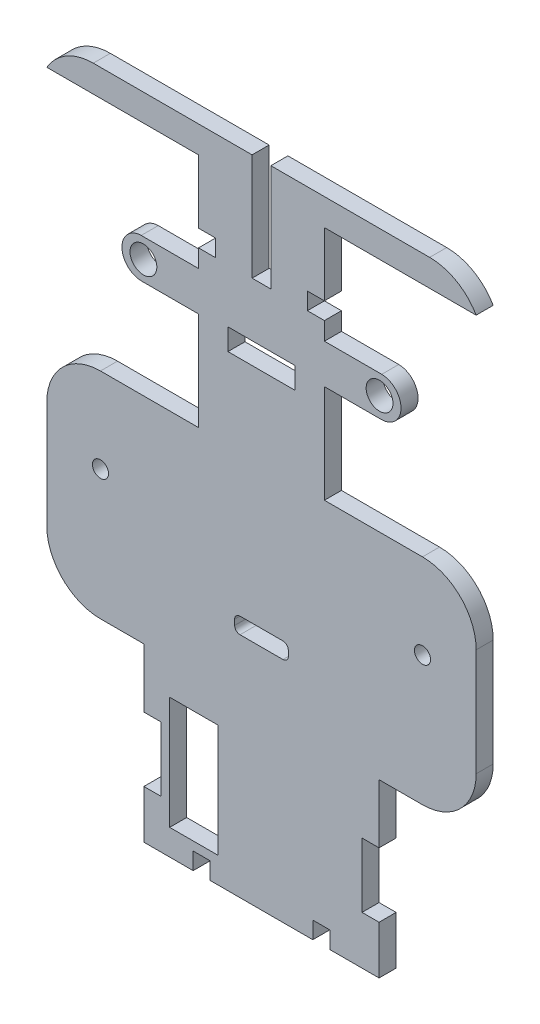
SolidWorks part; units mm, degrees
ref_plane "Front Plane" through (0, 0, 0) normal (0, 0, 1) x (1, 0, 0)
ref_plane "Top Plane" through (0, 0, 0) normal (0, 1, 0) x (1, 0, 0)
ref_plane "Right Plane" through (0, 0, 0) normal (1, 0, 0) x (0, 0, -1)
sketch "Sketch1" plane through (0, 0, 0) normal (0, 0, 1) x (1, 0, 0)
  line L0 (0, 41.2415) -> (0, -44.2517) construction
  line L1 (-63.3907, 0) -> (63.762, 0) construction
  line L2 (-9.56, -41.4376) -> (9.56, -41.4376)
  line L3 (21.91, -41.4376) -> (21.91, -32.4376)
  line L4 (21.91, -9.4376) -> (40, -9.4376)
  line L5 (40, -9.4376) -> (40, 30.5624)
  line L6 (40, 30.5624) -> (10, 30.5624)
  line L7 (10, 30.5624) -> (10, 45.5624)
  line L8 (12.735, -31.7231) -> (12.735, -41.4376) construction
  line L9 (-10, 59.5624) -> (-8.5528, 59.5624)
  line L10 (10, 59.5624) -> (8.5528, 59.5624)
  line L11 (11.7278, 62.7374) -> (11.7278, 74.5624)
  line L12 (11.7278, 74.5624) -> (40, 74.5624)
  line L13 (40, 74.5624) -> (40, 79.5624)
  line L14 (-40, 79.5624) -> (40, 79.5624)
  line L15 (0, 41.2415) -> (0, 85.4214) construction
  line L16 (22, 52.5624) -> (-14.5, 52.5624) construction
  line L17 (8.5528, 59.5624) -> (8.5528, 62.7374)
  line L18 (8.5528, 62.7374) -> (11.7278, 62.7374)
  line L19 (15.91, -41.4376) -> (21.91, -41.4376)
  line L20 (12.735, -41.4376) -> (12.735, -38.2626)
  line L21 (22, 50.0624) -> (22, 45.5624) construction
  line L22 (-10, 45.5624) -> (-10, 48.8958)
  line L23 (12.735, -38.2626) -> (9.56, -38.2626)
  line L24 (21.91, -20.4376) -> (21.91, -9.4376)
  line L25 (10, 59.5624) -> (-10, 59.5624) construction
  line L26 (21.91, -20.4376) -> (18.735, -20.4376)
  line L27 (18.735, -20.4376) -> (18.735, -32.4376)
  line L28 (18.735, -32.4376) -> (21.91, -32.4376)
  line L29 (9.56, -38.2626) -> (9.56, -41.4376)
  line L30 (12.735, -41.4376) -> (15.91, -41.4376)
  line L31 (21.91, -9.4376) -> (21.91, 2.5624) construction
  line L32 (-11.7278, 56.229) -> (-22.4103, 56.229)
  line L33 (-12.735, -31.7231) -> (-12.735, -41.4376) construction
  line L34 (11.7278, 62.7374) -> (11.7278, 56.229) construction
  line L35 (-19.5, 52.5624) -> (-22, 52.5624) construction
  line L36 (-12.735, -41.4376) -> (-15.91, -41.4376)
  line L37 (-9.56, -38.2626) -> (-9.56, -41.4376)
  line L38 (-18.735, -32.4376) -> (-21.91, -32.4376)
  line L39 (-18.735, -20.4376) -> (-18.735, -32.4376)
  line L40 (-21.91, -20.4376) -> (-18.735, -20.4376)
  line L41 (-21.91, -20.4376) -> (-21.91, -9.4376)
  line L42 (-12.735, -38.2626) -> (-9.56, -38.2626)
  line L43 (10, 59.5624) -> (11.7278, 59.5624)
  line L44 (11.7278, 59.5624) -> (11.7278, 56.229)
  line L45 (-12.735, -41.4376) -> (-12.735, -38.2626)
  line L46 (-15.91, -41.4376) -> (-21.91, -41.4376)
  line L47 (-8.5528, 62.7374) -> (-11.7278, 62.7374)
  line L48 (-8.5528, 59.5624) -> (-8.5528, 62.7374)
  line L49 (-40, 74.5624) -> (-40, 79.5624)
  line L50 (-11.7278, 74.5624) -> (-40, 74.5624)
  line L51 (-11.7278, 62.7374) -> (-11.7278, 74.5624)
  line L52 (-10, 59.5624) -> (-8.5528, 59.5624)
  line L53 (-11.7278, 59.5624) -> (-11.7278, 56.229)
  line L54 (-10, 30.5624) -> (-10, 45.5624)
  line L55 (-40, 30.5624) -> (-10, 30.5624)
  line L56 (-40, -9.4376) -> (-40, 30.5624)
  line L57 (-21.91, -9.4376) -> (-40, -9.4376)
  line L58 (-21.91, -41.4376) -> (-21.91, -32.4376)
  line L59 (10, 45.5624) -> (10, 56.229) construction
  line L60 (22, 45.5624) -> (31.5207, 45.5624) construction
  line L61 (-10, 48.8958) -> (-22.4103, 48.8958)
  line L62 (22, 55.0624) -> (22, 59.5624) construction
  line L63 (-10, 59.5624) -> (-11.7278, 59.5624)
  line L64 (18.8205, 56.229) -> (11.7278, 56.229) construction
  line L65 (18.8205, 48.8958) -> (10, 48.8958) construction
  line L66 (22, 47.9767) -> (26, 47.9767) construction
  line L67 (18.8205, 48.8958) -> (22.4103, 48.8958) construction
  line L68 (26, 47.9767) -> (26, 56.3586) construction
  line L69 (18.8205, 56.229) -> (26, 56.229) construction
  line L70 (21.91, 2.5624) -> (-21.91, 2.5624) construction
  line L71 (11.7278, 56.229) -> (22.4103, 56.229)
  line L72 (10, 45.5624) -> (10, 48.8958)
  line L73 (10, 48.8958) -> (22.4103, 48.8958)
  line L74 (-21.91, 2.5624) -> (-21.91, -9.4376) construction
  line L76 (-4, 1) -> (4, 1)
  line L77 (-5, 2) -> (-5, 3)
  line L78 (-4, 4) -> (4, 4)
  line L79 (5, 2) -> (5, 3)
  line L80 (-5, 1) -> (5, 4) construction
  line L81 (-5, 4) -> (5, 1) construction
  circle A0 centre (-22, 52.5624) radius 2.5
  arc A1 (4, 4) -> (5, 3) centre (4, 3) cw
  arc A2 (22.4103, 56.229) -> (22.4103, 48.8958) centre (22.3326, 52.5624) cw
  circle A3 centre (22, 52.5624) radius 2.5
  arc A4 (-22.4103, 56.229) -> (-22.4103, 48.8958) centre (-22.3326, 52.5624) ccw
  arc A5 (5, 2) -> (4, 1) centre (4, 2) cw
  arc A6 (-4, 1) -> (-5, 2) centre (-4, 2) cw
  arc A7 (-5, 3) -> (-4, 4) centre (-4, 3) cw
  spline S1 degree 1 poles (0, 79.5624) (40, 79.5624) knots 0 0 1 1
  spline S2 degree 1 poles (0, 79.5624) (-40, 79.5624) knots 0 0 1 1
  point P23 (10, 38.0624)
  point P26 (0, 2.5)
  point P45 (0, 59.5624)
  point P46 (0, 52.5624)
  point P71 (0, 79.5624)
  point P77 (0, -41.4376)
  dimension "D12" = 10
  dimension "D13" = 1
  dimension "D6" = 40
  dimension "D1" = 21.91
  dimension "D2" = 32
  dimension "D3" = 40
  dimension "D4" = 18.09
  dimension "D5" = 15
  dimension "D7" = 12
  dimension "D8" = 5
  dimension "D9" = 9.175
  dimension "D10" = 3
  dimension "D11" = 10
  dimension "D14" = 21.5207
  dimension "D15" = 3.175
  dimension "D16" = 9
  dimension "D17" = 12
  dimension "D18" = 3.175
  dimension "D19" = 3.175
  dimension "D20" = 3.175
  dimension "D21" = 3.175
  dimension "D22" = 4
  dimension "D23" = 2.5
extrude "Boss-Extrude1" add sketch "Sketch1" along normal blind 3.175 contours L54 L55 L56 L57 L41 L40 L39 L38 L58 L46 L36 L45 L42 L37 L2 L29 L23 L20 L30 L19 L3 L28 L27 L26 L24 L4 L5 L6 L7 L32 L10 L17 L18 L11 L12 L13 L14 L49 L50 region at (0, 15.129, 0)
fillet "Fillet1" radius 10 2 edges at (-40, 79.5624, 1.5875) (40, 79.5624, 1.5875)
sketch "Sketch2" plane through (0, 0, 3.175) normal (0, 0, 1) x (1, 0, 0)
  line L0 (-21.91, -36.6376) -> (21.91, -36.6376) construction
  line L1 (-21.91, -41.4376) -> (-21.91, -32.4376) construction
  line L2 (21.91, -41.4376) -> (21.91, -32.4376) construction
  line L3 (-12.735, -41.4376) -> (-21.91, -41.4376) construction
  line L4 (-17.11, -41.4376) -> (-17.11, -8.6603) construction
  line L6 (-17.11, -36.6376) -> (-8.11, -36.6376)
  line L7 (-17.11, -36.6376) -> (-17.11, -15.6376)
  line L8 (-17.11, -15.6376) -> (-8.11, -15.6376)
  line L9 (-8.11, -36.6376) -> (-8.11, -15.6376)
  dimension "D1" = 4.8
  dimension "D2" = 4.8
  dimension "D3" = 21
  dimension "D4" = 9
extrude "Cut-Extrude1" cut sketch "Sketch2" against normal through all
sketch "Sketch3" plane through (0, 0, 3.175) normal (0, 0, 1) x (1, 0, 0)
  line L0 (0, 0) -> (0, 79.5624) construction
  line L2 (-10, 45.5624) -> (10, 45.5624) construction
  line L3 (-7.7407, 59.5624) -> (8.5528, 59.5624) construction
  line L6 (-1.75, 59.6631) -> (1.75, 59.6631)
  line L7 (-1.75, 59.6631) -> (-1.75, 79.6631)
  line L8 (-1.75, 79.6631) -> (1.75, 79.6631)
  line L9 (1.75, 59.6631) -> (1.75, 79.6631)
  line L10 (-1.75, 59.6631) -> (1.75, 79.6631) construction
  line L11 (-1.75, 79.6631) -> (1.75, 59.6631) construction
  line L12 (-6.25, 45.5624) -> (6.25, 45.5624)
  line L13 (-6.25, 45.5624) -> (-6.25, 49.5624)
  line L14 (-6.25, 49.5624) -> (6.25, 49.5624)
  line L15 (6.25, 45.5624) -> (6.25, 49.5624)
  line L16 (-6.25, 45.5624) -> (6.25, 49.5624) construction
  line L17 (-6.25, 49.5624) -> (6.25, 45.5624) construction
  point P14 (0, 69.6631)
  point P19 (0, 47.5624)
  dimension "D1" = 3.5
  dimension "D2" = 20
  dimension "D3" = 0
  dimension "D4" = 4
  dimension "D5" = 12.5
extrude "Cut-Extrude2" cut sketch "Sketch3" against normal through all contours L12 L15 L14 L13 | L7 L8 L9 L6 region at (0, 47.5624, 3.175)
fillet "Fillet2" radius 10 4 edges at (-40, -9.4376, 1.5875) (40, -9.4376, 1.5875) (40, 30.5624, 1.5875) (-40, 30.5624, 1.5875)
sketch "Sketch4" plane through (0, 59.5624, 0) normal (0, 1, 0) x (1, 0, 0)
  line L4 (11.7278, 0) -> (8.5528, 0)
  line L5 (8.5528, 0) -> (8.5528, -3.175)
  line L6 (8.5528, -3.175) -> (11.7278, -3.175)
  line L7 (11.7278, -3.175) -> (11.7278, 0)
  line L8 (11.7278, 0) -> (8.5528, 0)
  line L9 (8.5528, 0) -> (8.5528, -3.175)
  line L10 (8.5528, -3.175) -> (11.7278, -3.175)
  line L11 (11.7278, -3.175) -> (11.7278, 0)
  dimension "D1" = 0
extrude "Boss-Extrude2" add sketch "Sketch4" against normal up to surface (29 mm away) up to face at (20, 30.5624, 1.5875)
sketch "Sketch5" plane through (0, 59.5624, 0) normal (0, 1, 0) x (1, 0, 0)
  line L4 (-8.5528, 0) -> (-11.7278, 0)
  line L5 (-11.7278, 0) -> (-11.7278, -3.175)
  line L6 (-11.7278, -3.175) -> (-8.5528, -3.175)
  line L7 (-8.5528, -3.175) -> (-8.5528, 0)
  line L8 (-8.5528, 0) -> (-11.7278, 0)
  line L9 (-11.7278, 0) -> (-11.7278, -3.175)
  line L10 (-11.7278, -3.175) -> (-8.5528, -3.175)
  line L11 (-8.5528, -3.175) -> (-8.5528, 0)
  dimension "D1" = 0
extrude "Boss-Extrude3" add sketch "Sketch5" against normal up to surface (29 mm away) up to face at (-20, 30.5624, 1.5875)
sketch "Sketch7" plane through (0, 0, 3.175) normal (0, 0, 1) x (1, 0, 0)
  circle A0 centre (-30, 14.7335) radius 1.5
  circle A1 centre (30, 14.7335) radius 1.5
  dimension "D1" = 3
  dimension "D2" = 3
extrude "Cut-Extrude3" cut sketch "Sketch7" against normal blind 10
